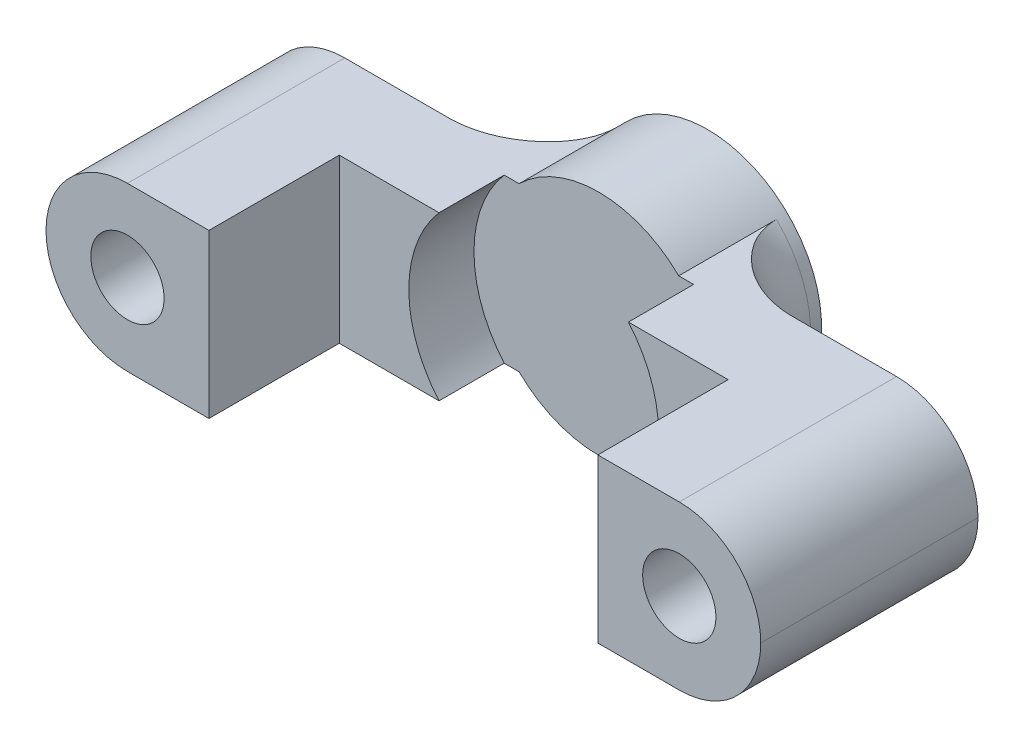
SolidWorks part; units mm, degrees
ref_plane "Front Plane" through (0, 0, 0) normal (0, 0, 1) x (1, 0, 0)
ref_plane "Top Plane" through (0, 0, 0) normal (0, 1, 0) x (1, 0, 0)
ref_plane "Right Plane" through (0, 0, 0) normal (1, 0, 0) x (0, 0, -1)
sketch "Sketch1" plane through (0, 0, 0) normal (0, 0, 1) x (1, 0, 0)
  line L0 (-38.1, 0) -> (38.1, 0) construction
  line L1 (-38.1, -7.5) -> (38.1, -7.5)
  line L2 (-38.1, -7.5) -> (-38.1, 7.5)
  line L3 (-38.1, 7.5) -> (38.1, 7.5)
  line L4 (38.1, -7.5) -> (38.1, 7.5)
  line L5 (-38.1, -7.5) -> (38.1, 7.5) construction
  line L6 (-38.1, 7.5) -> (38.1, -7.5) construction
  circle A0 centre (0, 0) radius 11.5
  circle A1 centre (-25.4, 0) radius 3.3734
  circle A2 centre (25.4, 0) radius 3.3734
  dimension "D1" = 23
  dimension "D5" = 6.7469
  dimension "D6" = 6.7469
  dimension "D2" = 25.4
  dimension "D3" = 25.4
  dimension "D4" = 76.2
  dimension "D7" = 15
extrude "Boss-Extrude1" add sketch "Sketch1" along normal blind 6 contours A0 L1 L4 L3 A2 | A0 L3 L2 L1 A1 region at (-37.7701, 0, 0) region at (11.0913, -4.1144, 0)
sketch "Sketch2" plane through (0, 0, 0) normal (0, 0, -1) x (-1, 0, 0)
  line L0 (8.7178, -7.5) -> (38.1, -7.5) construction
  line L1 (38.1, -7.5) -> (38.1, 7.5) construction
  line L2 (38.1, 7.5) -> (8.7178, 7.5) construction
  line L3 (-8.7178, 7.5) -> (-38.1, 7.5) construction
  line L4 (-38.1, 7.5) -> (-38.1, -7.5) construction
  line L5 (-38.1, -7.5) -> (-8.7178, -7.5) construction
  line L6 (8.7178, -7.5) -> (38.1, -7.5)
  line L7 (38.1, -7.5) -> (38.1, 7.5)
  line L8 (38.1, 7.5) -> (8.7178, 7.5)
  line L9 (-8.7178, 7.5) -> (-38.1, 7.5)
  line L10 (-38.1, 7.5) -> (-38.1, -7.5)
  line L11 (-38.1, -7.5) -> (-8.7178, -7.5)
  line L13 (-38.1, -7.5) -> (38.1, -7.5)
  line L14 (-38.1, -7.5) -> (-38.1, 7.5)
  line L15 (-38.1, 7.5) -> (38.1, 7.5)
  line L16 (38.1, -7.5) -> (38.1, 7.5)
  line L17 (-38.1, -7.5) -> (38.1, 7.5) construction
  line L18 (-38.1, 7.5) -> (38.1, -7.5) construction
  arc A0 (8.7178, -7.5) -> (8.7178, 7.5) centre (0, 0) ccw construction
  arc A1 (-8.7178, 7.5) -> (-8.7178, -7.5) centre (0, 0) ccw construction
  circle A2 centre (25.4, 0) radius 3.3734 construction
  circle A3 centre (-25.4, 0) radius 3.3734 construction
  arc A4 (8.7178, -7.5) -> (8.7178, 7.5) centre (0, 0) ccw
  arc A5 (-8.7178, 7.5) -> (-8.7178, -7.5) centre (0, 0) ccw
  circle A6 centre (25.4, 0) radius 3.3734
  circle A7 centre (-25.4, 0) radius 3.3734
  circle M1 centre (-25.4, 0) radius 3.3734
  arc M2 (-8.7178, -7.5) -> (-8.7178, 7.5) centre (0, 0) cw
  line M3 (-8.7178, 7.5) -> (-38.1, 7.5)
  line M4 (-38.1, 7.5) -> (-38.1, -7.5)
  line M5 (-38.1, -7.5) -> (-8.7178, -7.5)
extrude "Boss-Extrude2" add sketch "Sketch2" along normal blind 2 contours M5 M2 M3 M4 M1 | L13 A4 L15 M2 | A4 L6 L7 L8 A6 region at (-11.8299, 0, 0) region at (0, 0, 0) region at (23.4089, -7.1701, 0)
sketch "Sketch3" plane through (0, 0, -2) normal (0, 0, -1) x (-1, 0, 0)
  circle A0 centre (0, 0) radius 10.5
  dimension "D1" = 21
extrude "Boss-Extrude3" add sketch "Sketch3" against normal blind 2
sketch "Sketch4" plane through (0, 0, -2) normal (0, 0, -1) x (-1, 0, 0)
  circle A0 centre (0, 0) radius 10.5
  circle A1 centre (0, 0) radius 1.5
  dimension "D1" = 3
extrude "Boss-Extrude4" add sketch "Sketch4" along normal blind 2 contours A0
sketch "Sketch5" plane through (0, 0, -4) normal (0, 0, -1) x (-1, 0, 0)
  circle A0 centre (0, 0) radius 1.5
  circle A1 centre (0, 0) radius 10.5
  dimension "D1" = 3
extrude "Boss-Extrude5" add sketch "Sketch5" along normal blind 6
fillet "Fillet1" radius 7 1 edges at (-10.5, 0, -2)
sketch "Sketch6" plane through (0, 0, 6) normal (0, 0, 1) x (1, 0, 0)
  line L0 (8.7178, -7.5) -> (38.1, -7.5) construction
  line L1 (17.9, 7.5) -> (32.9, 7.5)
  line L2 (17.9, 7.5) -> (17.9, -7.5)
  line L3 (17.9, -7.5) -> (32.9, -7.5)
  line L4 (32.9, 7.5) -> (32.9, -7.5)
  line L5 (17.9, 7.5) -> (32.9, -7.5) construction
  line L6 (17.9, -7.5) -> (32.9, 7.5) construction
  circle A0 centre (25.4, 0) radius 3.3734 construction
  circle A1 centre (25.4, 0) radius 3.3734
  point P0 (25.4, 0)
  dimension "D1" = 15
extrude "Boss-Extrude6" add sketch "Sketch6" along normal blind 12
sketch "Sketch7" plane through (0, 0, -2) normal (0, 0, -1) x (-1, 0, 0)
  circle A0 centre (-25.4, 0) radius 5.5
  dimension "D1" = 11
extrude "Cut-Extrude2" cut sketch "Sketch7" against normal blind 15
sketch "Sketch8" plane through (38.1, 0, 0) normal (1, 0, 0) x (0, 0, -1)
  line L4 (-6, -7.5) -> (2, -7.5)
  line L5 (2, -7.5) -> (2, 7.5)
  line L6 (2, 7.5) -> (-6, 7.5)
  line L7 (-6, 7.5) -> (-6, -7.5)
  line L8 (-6, -7.5) -> (2, -7.5)
  line L9 (2, -7.5) -> (2, 7.5)
  line L10 (2, 7.5) -> (-6, 7.5)
  line L11 (-6, 7.5) -> (-6, -7.5)
  dimension "D1" = 0
extrude "Cut-Extrude3" cut sketch "Sketch8" against normal up to surface (5.2 mm away) up to face at (32.9, 0, 12)
mirror "Mirror1" about plane through (0, 0, 0) normal (1, 0, 0) of "Cut-Extrude2", "Boss-Extrude6"
sketch "Sketch9" plane through (-38.1, 0, 0) normal (-1, 0, 0) x (0, 0, 1)
  line L4 (-2, -7.5) -> (6, -7.5)
  line L5 (6, -7.5) -> (6, 7.5)
  line L6 (6, 7.5) -> (-2, 7.5)
  line L7 (-2, 7.5) -> (-2, -7.5)
  line L8 (-2, -7.5) -> (6, -7.5)
  line L9 (6, -7.5) -> (6, 7.5)
  line L10 (6, 7.5) -> (-2, 7.5)
  line L11 (-2, 7.5) -> (-2, -7.5)
  dimension "D1" = 0
extrude "Cut-Extrude4" cut sketch "Sketch9" against normal up to surface (5.2 mm away) up to face at (-32.9, 0, 12)
fillet "Fillet2" radius 7.5 4 edges at (32.9, -7.5, 8) (32.9, 7.5, 8) (-32.9, 7.5, 8) (-32.9, -7.5, 8)
